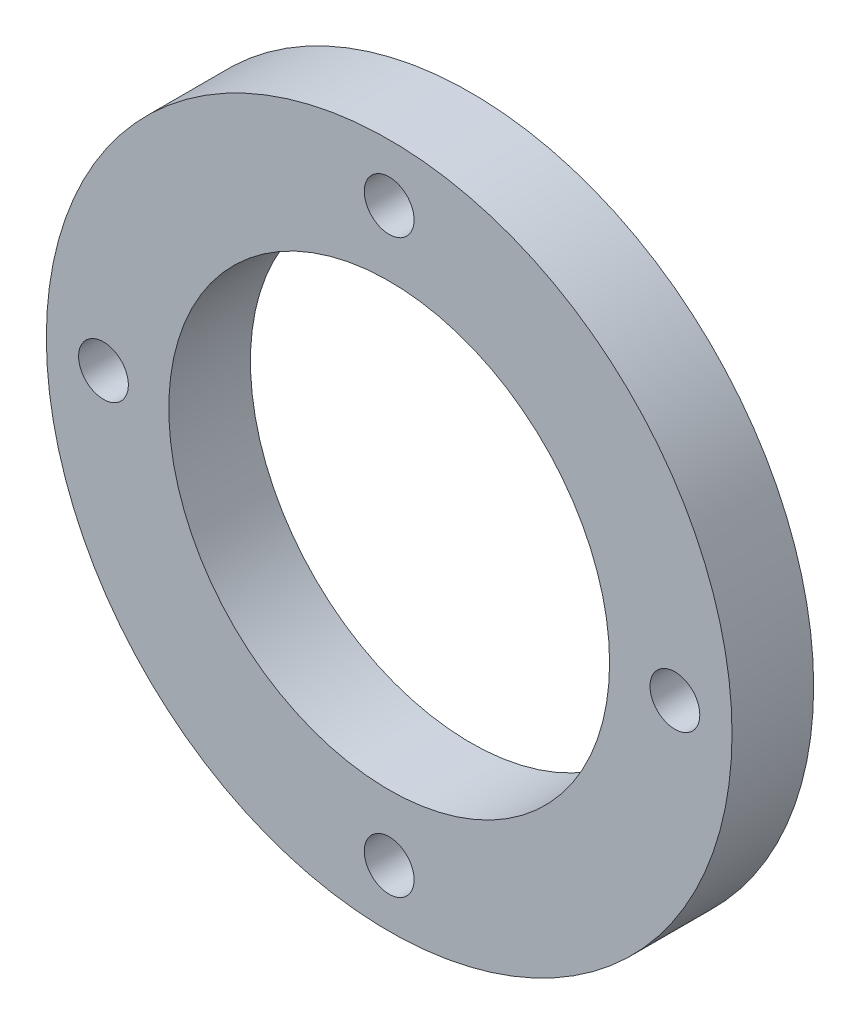
SolidWorks part; units mm, degrees
material "6061 Alloy"
ref_plane "Front Plane" through (0, 0, 0) normal (0, 0, 1) x (1, 0, 0)
ref_plane "Top Plane" through (0, 0, 0) normal (0, 1, 0) x (1, 0, 0)
ref_plane "Right Plane" through (0, 0, 0) normal (1, 0, 0) x (0, 0, -1)
sketch "Sketch1" plane through (0, 0, 0) normal (0, 0, 1) x (1, 0, 0)
  circle A5 centre (49, 5) radius 13
  circle A6 centre (31.5, 5) radius 1.5
  circle A7 centre (49, 22.5) radius 1.5
  circle A8 centre (66.5, 5) radius 1.5
  circle A9 centre (49, -12.5) radius 1.5
  arc A10 (49, -16) -> (49, 26) centre (49, 5) ccw construction
  circle A11 centre (49, 5) radius 21
  dimension "D1" = 3
  dimension "D2" = 26
  dimension "D3" = 31.5
  dimension "D4" = 66.5
  dimension "D5" = 22.5
  dimension "D6" = 12.5
extrude "Boss-Extrude1" add sketch "Sketch1" along normal blind 5
sketch "Sketch2" plane through (0, 0, 5) normal (0, 0, 1) x (1, 0, 0)
  circle A0 centre (49, 5) radius 13.5
  dimension "D1" = 27
extrude "Cut-Extrude1" cut sketch "Sketch2" against normal blind 10
sketch "Sketch3" plane through (0, 0, 5) normal (0, 0, 1) x (1, 0, 0)
  circle A0 centre (49, 22.5) radius 1.525
  circle A1 centre (31.5, 5) radius 1.525
  circle A2 centre (66.5, 5) radius 1.525
  circle A3 centre (49, -12.5) radius 1.525
  dimension "D1" = 3.05
extrude "Cut-Extrude2" cut sketch "Sketch3" against normal blind 10
